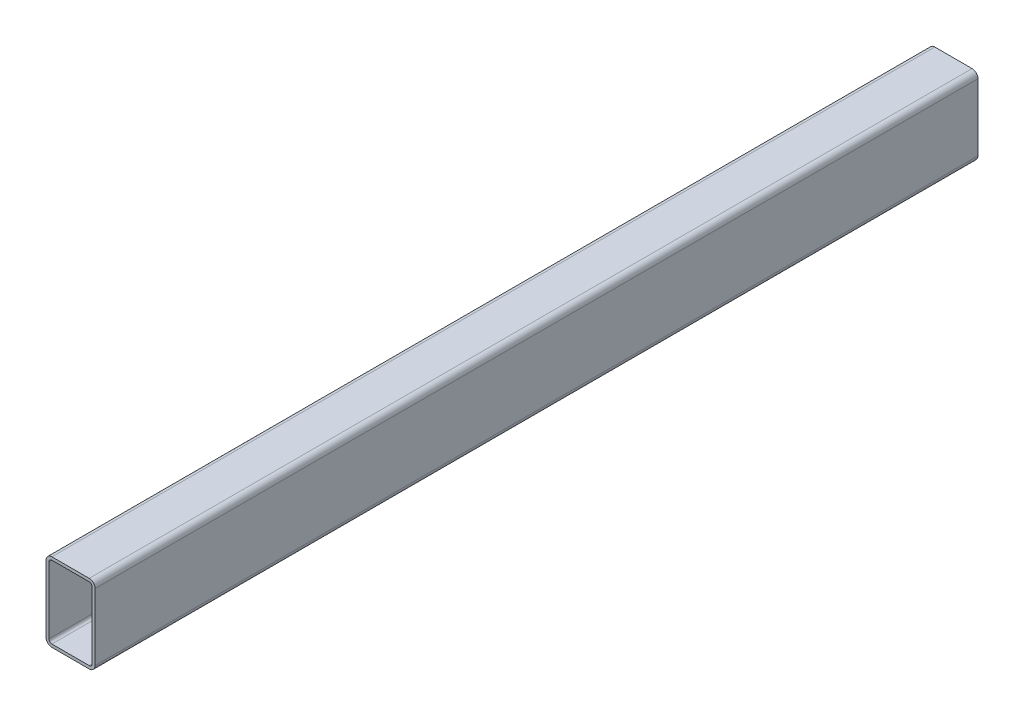
SolidWorks part; units mm, degrees
ref_plane "Front Plane" through (0, 0, 0) normal (0, 0, 1) x (1, 0, 0)
ref_plane "Top Plane" through (0, 0, 0) normal (0, 1, 0) x (1, 0, 0)
ref_plane "Right Plane" through (0, 0, 0) normal (1, 0, 0) x (0, 0, -1)
sketch "Sketch1" plane through (0, 0, 0) normal (0, 0, 1) x (1, 0, 0)
  line L0 (19, 37) -> (-19, 37)
  line L1 (19, -40) -> (-19, -40)
  line L2 (25, -34) -> (25, 34)
  line L3 (19, 40) -> (-19, 40)
  line L4 (-25, -34) -> (-25, 34)
  line L5 (25, -40) -> (-25, 40) construction
  line L6 (25, 40) -> (-25, -40) construction
  line L7 (-22, -34) -> (-22, 34)
  line L8 (19, -37) -> (-19, -37)
  line L9 (22, -34) -> (22, 34)
  arc A0 (-19, -40) -> (-25, -34) centre (-19, -34) cw
  arc A1 (19, -40) -> (25, -34) centre (19, -34) ccw
  arc A2 (25, 34) -> (19, 40) centre (19, 34) ccw
  arc A3 (-19, 40) -> (-25, 34) centre (-19, 34) ccw
  arc A4 (-19, 37) -> (-22, 34) centre (-19, 34) ccw
  arc A5 (-19, -37) -> (-22, -34) centre (-19, -34) cw
  arc A6 (19, -37) -> (22, -34) centre (19, -34) ccw
  arc A7 (22, 34) -> (19, 37) centre (19, 34) ccw
  point P0 (0, 0)
  dimension "D1" = 6
  dimension "D3" = 80
  dimension "D4" = 50
  dimension "D2" = 3
extrude "Boss-Extrude1" add sketch "Sketch1" along normal mid plane 900
equation "\"M5_tap\"=4.2mm       ' Below you can do mesurements as follows: cm, mm, ft, in, m, "
equation "\"M5_clearence\"=5.5mm"
equation "\"M6_tap\"=5mm"
equation "\"M6_clearence\"=6.6mm"
equation "\"work_area_width\"=1100mm"
equation "\"work_area_depth\"=900mm"
equation "\"D3@Sketch1\"=\"steel_sides_width\""
equation "\"D4@Sketch1\"=\"steel_sides_height\""
equation "\"D1@Sketch1\"=\"steel_sides_radius\""
equation "\"D2@Sketch1\"=\"steel_sides_wall_thickness\""
equation "\"D1@Boss-Extrude1\"=\"work_area_depth\""
equation "\"steel_base_width\"=80mm"
equation "\"steel_base_height\"=50mm"
equation "\"steel_base_wall_thickness\"=3mm"
equation "\"steel_base_radius\"=6mm"
equation "\"steel_sides_width\"=80mm    'this tube is rotated so flip width/height"
equation "\"steel_sides_height\"=50mm    'this tube is rotated so flip width/height"
equation "\"steel_sides_wall_thickness\"=3mm"
equation "\"steel_sides_radius\"=6mm"
equation "\"steel_gantry_width\"=80mm    'this tube is rotated so flip width/height"
equation "\"steel_gantry_height\"=50mm    'this tube is rotated so flip width/height"
equation "\"steel_gantry_wall_thickness\"=3mm"
equation "\"steel_gantry_radius\"=6mm"
equation "\"steel_rollers_width\"=80mm"
equation "\"steel_rollers_height\"=50mm    'keep as low as possible as this increases how big plastic parts are"
equation "\"steel_rollers_wall_thickness\"=3mm"
equation "\"steel_rollers_radius\"=6mm"
equation "\"steel_zbox_width\"=80mm     'if the gantry height (rotated) is too thick, a wider zbox is necessary"
equation "\"steel_zbox_height\"=50mm    'hole patteren changes as the zbox and gantry height (rotated) changes."
equation "\"steel_zbox_wall_thickness\"=3mm"
equation "\"steel_zbox_radius\"=6mm"
equation "\"alu_zangle_width\"=80mm     'check that it doesn't interfer with the gantry"
equation "\"alu_zangle_height\"=50mm"
equation "\"alu_zangle_wall_thickness\"=7mm  'check that it doesn't interfer with the gantry"
